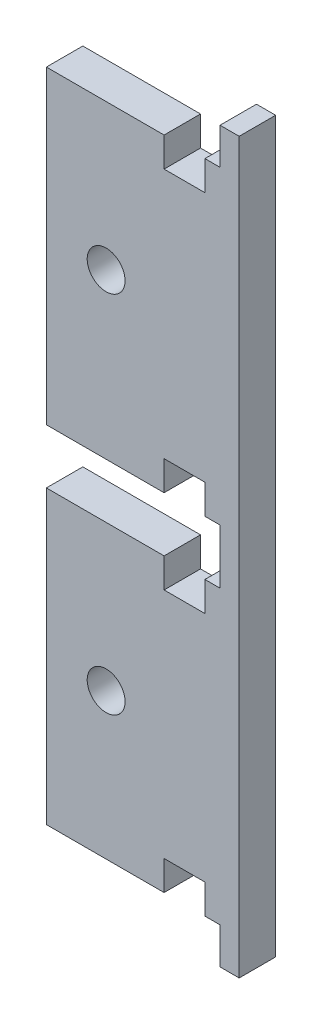
SolidWorks part; units mm, degrees
material "AISI 4130 Steel, annealed at 865C"
ref_plane "X-Y Datum" through (0, 0, 0) normal (0, 0, 1) x (1, 0, 0)
ref_plane "X-Z Datum" through (0, 0, 0) normal (0, 1, 0) x (1, 0, 0)
ref_plane "Y-Z Datum" through (0, 0, 0) normal (1, 0, 0) x (0, 0, -1)
sketch "Sketch2" plane through (0, 0, 0) normal (0, 0, 1) x (1, 0, 0)
  line L0 (34.925, 127) -> (0, 127) construction
  line L1 (0, 0) -> (40.64, 0)
  line L2 (0, 0) -> (0, 127)
  line L3 (0, 127) -> (40.64, 127)
  line L4 (40.64, 0) -> (40.64, 127)
  point P7 (17.4625, 31.75)
  point P8 (17.4625, 95.25)
  dimension "D1" = 40.64
extrude "Boss-Extrude1" add sketch "Sketch2" along normal blind 6.35
hole_wizard "M6 Clearance Hole1" positions "Sketch3" profile "Sketch4" hole size "M6" standard "ANSI Metric" end condition through all
sketch "Sketch3" plane through (0, 0, 6.35) normal (0, 0, 1) x (1, 0, 0)
  point P0 (17.4625, 31.75)
  point P3 (17.4625, 95.25)
sketch "Sketch4" plane through (17.4625, 31.75, 6.35) normal (1, 0, 0) x (0, -1, 0)
  line L0 (0, 0) -> (0, 6.35)
  line L1 (0, 6.35) -> (3.3, 6.35)
  line L2 (3.3, 6.35) -> (3.3, 0)
  line L5 (3.3, 0) -> (0, 0)
  line L11 (0, -6.35) -> (0, 107.95) construction
  dimension "Thru Hole Dia." = 6.6
  dimension "Thru Hole Depth" = 6.35
sketch "Sketch5" plane through (0, 0, 6.35) normal (0, 0, 1) x (1, 0, 0)
  line L0 (7.0505, 127) -> (7.0505, 0)
  line L1 (40.64, 127) -> (0, 127) construction
  line L2 (0, 0) -> (40.64, 0) construction
  circle A0 centre (17.4625, 95.25) radius 3.3 construction
  point P6 (14.1625, 95.25)
  line M4 (0, 127) -> (0, 0)
  line M5 (0, 0) -> (40.64, 0)
  line M7 (40.64, 127) -> (0, 127)
  dimension "D1" = 7.112
extrude "Cut-Extrude1" cut sketch "Sketch5" against normal through all and the other way through all contours L0 M7 M4 M5 region at (3.5252, 63.5, 6.35)
sketch "Sketch6" plane through (0, 0, 6.35) normal (0, 0, 1) x (1, 0, 0)
  line L0 (-3.175, 120.65) -> (38.1, 120.65)
  line L1 (38.1, 120.65) -> (38.1, 130.175)
  line L2 (38.1, 130.175) -> (-3.175, 130.175)
  line L3 (-3.175, 130.175) -> (-3.175, 120.65)
  line L4 (0, 123.825) -> (34.925, 123.825)
  line L5 (34.925, 123.825) -> (34.925, 127)
  line L6 (34.925, 127) -> (0, 127)
  line L7 (0, 127) -> (0, 123.825)
  line L8 (0, 123.825) -> (34.925, 123.825)
  line L9 (34.925, 123.825) -> (34.925, 127)
  line L10 (34.925, 127) -> (0, 127)
  line L11 (0, 127) -> (0, 123.825)
  line L12 (0, 60.325) -> (34.925, 60.325)
  line L13 (34.925, 60.325) -> (34.925, 63.5)
  line L14 (34.925, 63.5) -> (0, 63.5)
  line L15 (0, 63.5) -> (0, 60.325)
  line L16 (0, 60.325) -> (34.925, 60.325)
  line L17 (34.925, 60.325) -> (34.925, 63.5)
  line L18 (34.925, 63.5) -> (0, 63.5)
  line L19 (0, 63.5) -> (0, 60.325)
  line L24 (0, 0) -> (34.925, 0)
  line L25 (34.925, 0) -> (34.925, 3.175)
  line L26 (34.925, 3.175) -> (0, 3.175)
  line L27 (0, 3.175) -> (0, 0)
  line L28 (38.1, 66.675) -> (-3.175, 66.675)
  line L29 (-3.175, 66.675) -> (-3.175, 57.15)
  line L30 (-3.175, 57.15) -> (38.1, 57.15)
  line L31 (38.1, 57.15) -> (38.1, 66.675)
  line L32 (38.1, 6.35) -> (-3.175, 6.35)
  line L33 (-3.175, 6.35) -> (-3.175, -3.175)
  line L34 (-3.175, -3.175) -> (38.1, -3.175)
  line L35 (38.1, -3.175) -> (38.1, 6.35)
  line L36 (37.3063, 127) -> (37.3063, 0)
  line L37 (40.64, 127) -> (7.0505, 127) construction
  line L38 (7.0505, 0) -> (40.64, 0) construction
  line M19 (7.0505, 127) -> (7.0505, 0)
  line M20 (7.0505, 0) -> (40.64, 0)
  line M22 (40.64, 127) -> (7.0505, 127)
  dimension "D5" = 2.3813
  dimension "D1" = 0
  dimension "D2" = 0
  dimension "D4" = 3.175
extrude "Cut-Extrude2" cut sketch "Sketch6" against normal through all contours L36 L9 L8 L0 M22 M19 | L8 L9 M22 M19 | L36 L28 L18 L17 L16 L30 M19 | L17 L18 L16 M19 | L36 L32 L26 L25 M19 M20 | L25 L26 M19 M20 region at (23.1953, 122.4692, 6.35) region at (20.9877, 125.4125, 6.35) region at (22.1784, 66.3578, 6.35) region at (20.9878, 61.9125, 6.35) region at (23.1953, 4.5308, 6.35) region at (20.9878, 1.5875, 6.35)
sketch "Sketch7" plane through (0, 0, 6.35) normal (0, 0, 1) x (1, 0, 0)
  line L0 (34.671, 115.5065) -> (27.559, 115.5065)
  line L5 (27.559, 121.031) -> (27.559, 115.5065)
  line L18 (34.29, 120.65) -> (27.94, 120.65)
  line L19 (34.29, 120.65) -> (34.29, 115.8875)
  line L20 (34.29, 115.8875) -> (27.94, 115.8875)
  line L21 (27.94, 120.65) -> (27.94, 115.8875)
  line L22 (34.29, 71.4375) -> (27.94, 71.4375)
  line L23 (34.29, 71.4375) -> (34.29, 66.675)
  line L24 (34.29, 66.675) -> (27.94, 66.675)
  line L25 (27.94, 71.4375) -> (27.94, 66.675)
  line L26 (34.29, 57.15) -> (27.94, 57.15)
  line L27 (34.29, 57.15) -> (34.29, 52.3875)
  line L28 (34.29, 52.3875) -> (27.94, 52.3875)
  line L29 (27.94, 57.15) -> (27.94, 52.3875)
  line L30 (34.29, 11.1125) -> (27.94, 11.1125)
  line L31 (34.29, 11.1125) -> (34.29, 6.35)
  line L32 (34.29, 6.35) -> (27.94, 6.35)
  line L33 (27.94, 11.1125) -> (27.94, 6.35)
  line L34 (34.671, 121.031) -> (27.559, 121.031)
  line L35 (34.671, 121.031) -> (34.671, 115.5065)
  line L36 (34.671, 66.294) -> (27.559, 66.294)
  line L37 (27.559, 71.8185) -> (27.559, 66.294)
  line L38 (34.671, 71.8185) -> (27.559, 71.8185)
  line L39 (34.671, 71.8185) -> (34.671, 66.294)
  line L40 (34.671, 52.0065) -> (27.559, 52.0065)
  line L41 (27.559, 57.531) -> (27.559, 52.0065)
  line L42 (34.671, 57.531) -> (27.559, 57.531)
  line L43 (34.671, 57.531) -> (34.671, 52.0065)
  line L44 (34.671, 5.969) -> (27.559, 5.969)
  line L45 (27.559, 11.4935) -> (27.559, 5.969)
  line L46 (34.671, 11.4935) -> (27.559, 11.4935)
  line L47 (34.671, 11.4935) -> (34.671, 5.969)
  point P40 (0, 0)
  point P41 (0, 0)
  line M4 (37.3063, 120.65) -> (7.0505, 120.65)
  line M6 (7.0505, 66.675) -> (37.3063, 66.675)
  line M8 (37.3063, 57.15) -> (7.0505, 57.15)
  line M10 (7.0505, 6.35) -> (37.3063, 6.35)
  dimension "D1" = 0.381
extrude "Cut-Extrude3" cut sketch "Sketch7" against normal through all contours L30 L33 L31 M10 | L47 L46 L45 L33 L30 L31 M10 | L47 L45 L44 M10 | L29 L28 L27 M8 | L43 L27 L28 L29 L41 L40 M8 | L43 L42 L41 M8 | L39 L37 L36 M6 | L22 L25 L23 M6 | L39 L38 L37 L25 L22 L23 M6 | L21 L20 L19 M4 | L35 L19 L20 L21 L5 L0 M4 | L35 L34 L5 M4 region at (31.115, 115.5943, 6.35) region at (31.115, 120.8405, 6.35) region at (31.115, 118.2687, 6.35) region at (31.115, 69.0563, 6.35) region at (31.115, 71.5253, 6.35) region at (31.115, 66.4845, 6.35) region at (31.115, 54.7688, 6.35) region at (34.4805, 57.0622, 6.35) region at (31.115, 57.3405, 6.35) region at (31.115, 8.7312, 6.35) region at (31.115, 11.2003, 6.35) region at (31.115, 6.1595, 6.35)
